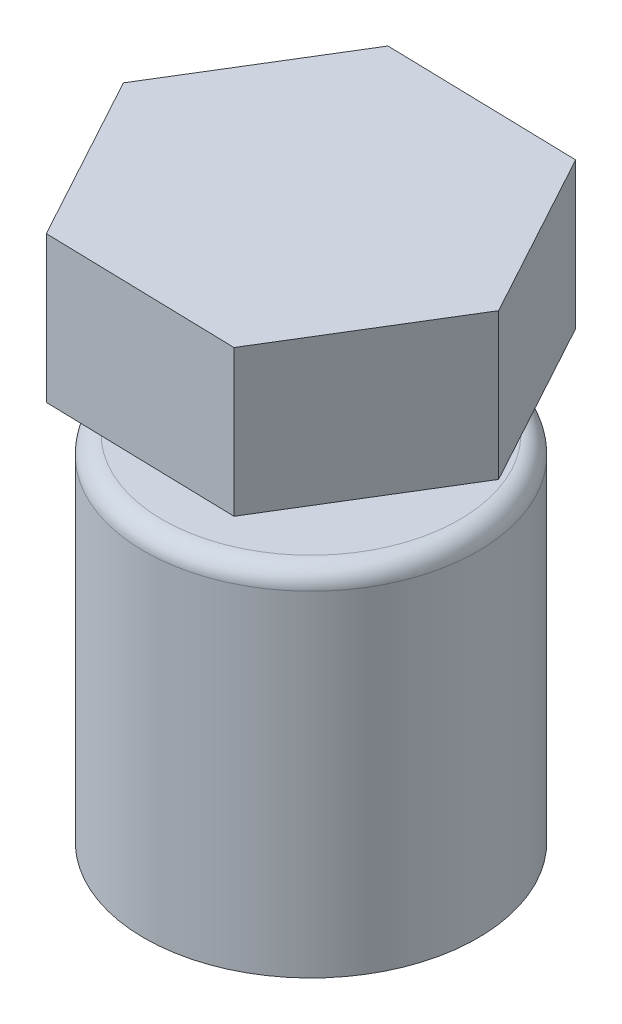
SolidWorks part; units mm, degrees
other "Cap"
other "Bottle"
ref_plane "Front Plane" through (0, 0, 0) normal (0, 0, 1) x (1, 0, 0)
ref_plane "Top Plane" through (0, 0, 0) normal (0, 1, 0) x (1, 0, 0)
ref_plane "Right Plane" through (0, 0, 0) normal (1, 0, 0) x (0, 0, -1)
sketch "Sketch1" plane through (0, 0, 0) normal (0, 0, 1) x (1, 0, 0)
  line L0 (0, 53.6444) -> (9.5369, 53.6444)
  line L1 (9.5369, 53.6444) -> (9.5369, 41.486)
  line L2 (9.5369, 41.486) -> (13.661, 41.486)
  line L3 (13.661, 41.486) -> (13.661, 27.5797)
  line L4 (13.661, 27.5797) -> (15.4447, 27.5797)
  line L5 (15.4447, 27.5797) -> (15.4447, 23.7134)
  line L6 (15.4447, 23.7134) -> (13.661, 23.7134)
  line L7 (13.661, 23.7134) -> (13.661, 11.3412)
  line L8 (13.661, 11.3412) -> (45.6225, 11.3412)
  line L9 (45.6225, 11.3412) -> (45.6225, -85.3166)
  line L10 (45.6225, -85.3166) -> (0, -85.3166)
  line L11 (0, -85.3166) -> (0, -75.7797)
  line L12 (0, -75.7797) -> (40.9829, -75.7797)
  line L13 (40.9829, -75.7797) -> (40.9829, 5.9283)
  line L14 (40.9829, 5.9283) -> (0, 5.9283)
  line L15 (0, 5.9283) -> (0, 53.6444)
revolve "Revolve1" add sketch "Sketch1" angle 360 about L15
fillet "Fillet1" radius 5 1 edges at (0, 11.3412, -45.6225)
sketch "Sketch2" plane through (0, 27.5797, 0) normal (0, 1, 0) x (1, 0, 0)
  line L1 (52.6638, -1.3196) -> (27.4747, 44.9484)
  line L2 (27.4747, 44.9484) -> (-25.1891, 46.268)
  line L3 (-25.1891, 46.268) -> (-52.6638, 1.3196)
  line L4 (-52.6638, 1.3196) -> (-27.4747, -44.9484)
  line L5 (-27.4747, -44.9484) -> (25.1891, -46.268)
  line L6 (25.1891, -46.268) -> (52.6638, -1.3196)
  circle A0 centre (0, 0) radius 45.6225 construction
  circle A1 centre (0, 0) radius 45.6225 construction
extrude "Boss-Extrude1" add sketch "Sketch2" along normal blind 40 separate body
revolve "Cut-Revolve1" cut sketch "Sketch1<2>" angle 360 about L15
sketch "Sketch1<2>" plane through (0, 0, 0) normal (0, 0, 1) x (1, 0, 0) same geometry as "Sketch1"
